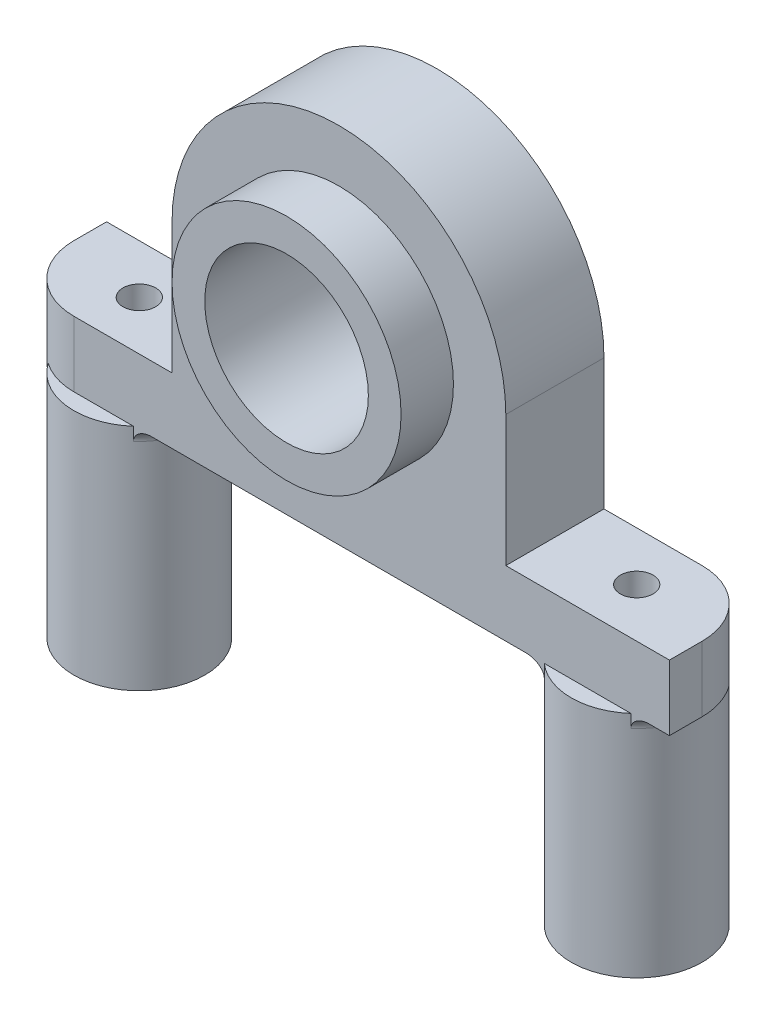
SolidWorks part; units mm, degrees
material "Plastique personnalisé"
ref_plane "Plan de face" through (0, 0, 0) normal (0, 0, 1) x (1, 0, 0)
ref_plane "Plan de dessus" through (0, 0, 0) normal (0, 1, 0) x (1, 0, 0)
ref_plane "Plan de droite" through (0, 0, 0) normal (1, 0, 0) x (0, 0, -1)
sketch "Esquisse1" plane through (0, 0, 0) normal (0, 0, 1) x (1, 0, 0)
  line L0 (-25.5, 30) -> (-25.5, 10)
  line L1 (-25.5, 10) -> (-50.5, 10)
  line L2 (-50.5, 10) -> (-50.5, 0)
  line L3 (-50.5, 0) -> (50.5, 0)
  line L4 (0, 6.4512) -> (0, -8.745) construction
  line L5 (50.5, 10) -> (50.5, 0)
  line L6 (25.5, 10) -> (50.5, 10)
  line L7 (25.5, 30) -> (25.5, 10)
  circle A0 centre (0, 30) radius 17.5
  circle A1 centre (0, 30) radius 12.5
  arc A2 (25.5, 30) -> (-25.5, 30) centre (0, 30) ccw
  point P14 (0, 0)
  dimension "D1" = 35
  dimension "D2" = 25
  dimension "D3" = 8
  dimension "D4" = 25
  dimension "D5" = 30
  dimension "D6" = 10
extrude "Boss.-Extru.1" add sketch "Esquisse1" along normal blind 15 contours L7 A2 L0 L1 L2 L3 L5 L6 A0 region at (0, 54.3476, 0)
extrude "Boss.-Extru.2" add sketch "Esquisse1<4>" along normal blind 23 contours A0 A1 region at (-17.005, 30, 0)
sketch "Esquisse1<4>" plane through (0, 0, 0) normal (0, 0, 1) x (1, 0, 0) same geometry as "Esquisse1"
sketch "Esquisse2" plane through (0, 10, 0) normal (0, 1, 0) x (1, 0, 0)
  line L0 (-50.5, -15) -> (-50.5, 0) construction
  line L1 (-25.5, -15) -> (-50.5, -15) construction
  line L2 (0, 9.676) -> (0, -6.0658) construction
  circle A0 centre (-38, -7.5) radius 2.5
  circle A1 centre (38, -7.5) radius 2.5
  dimension "D1" = 5
  dimension "D2" = 12.5
  dimension "D3" = 7.5
extrude "Enlèv. mat.-Extru.1" cut sketch "Esquisse2" against normal blind 25
fillet "Congé1" radius 10 2 edges at (50.5, 5, 0) (-50.5, 5, 15)
sketch "Esquisse3" plane through (0, 0, 0) normal (0, -1, 0) x (1, 0, 0)
  circle A0 centre (38, 7.5) radius 10
  circle A1 centre (-38, 7.5) radius 10
  circle A2 centre (-38, 7.5) radius 2.5
  circle A3 centre (38, 7.5) radius 2.5
  dimension "D1" = 20
  dimension "D2" = 5
extrude "Boss.-Extru.3" add sketch "Esquisse3" along normal blind 35
fillet "Congé2" radius 2 4 edges at (47.9279, 0, 8.699) (28, 0, 7.5) (-28, 0, 7.5) (-47.9279, 0, 6.301)
